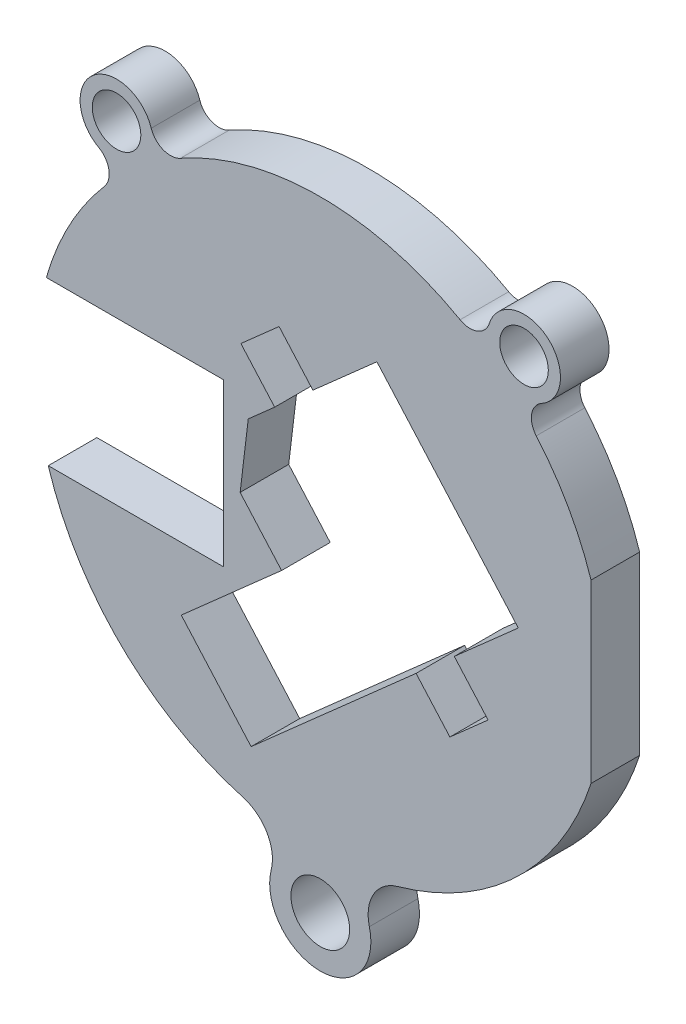
SolidWorks part; units mm, degrees
ref_plane "Front Plane" through (0, 0, 0) normal (0, 0, 1) x (1, 0, 0)
ref_plane "Top Plane" through (0, 0, 0) normal (0, 1, 0) x (1, 0, 0)
ref_plane "Right Plane" through (0, 0, 0) normal (1, 0, 0) x (0, 0, -1)
sketch "Sketch1" plane through (0, 0, 0) normal (0, 0, 1) x (1, 0, 0)
  line L0 (-21.141, 18.2245) -> (20.1141, 18.2245) construction
  line L1 (-4.8006, 1.8415) -> (-4.8006, -3.0861)
  line L2 (-4.8006, -3.0861) -> (-8.9662, -3.0861)
  line L3 (-8.9662, -3.0861) -> (-8.9662, -5.3514)
  line L4 (-8.9662, -5.3514) -> (-6.5786, -5.3514)
  line L5 (-4.9806, 7.3918) -> (-2.5835, 9.5123)
  line L6 (-2.5835, 9.5123) -> (-0.463, 7.1152)
  line L7 (-4.9806, 7.3918) -> (-2.8601, 4.9947)
  line L8 (3.2088, 10.3632) -> (-4.5153, 3.5306)
  line L9 (12.0777, 0.3371) -> (4.3536, -6.4955)
  line L10 (-4.5153, 3.5306) -> (-5.0276, -0.7207)
  line L11 (-5.0276, -0.7207) -> (0.0716, -6.4852)
  line L12 (0.0716, -6.4852) -> (4.3536, -6.4955)
  line L13 (-2.478, -3.6029) -> (7.6432, 5.3502) construction
  line L14 (3.2088, 10.3632) -> (12.0777, 0.3371)
  line L15 (3.2088, 10.3632) -> (11.8761, 18.0302)
  line L16 (-9.2588, -8.622) -> (-4.7522, -4.6355) construction
  line L17 (-9.2588, -8.622) -> (-5.994, -12.3128) construction
  line L18 (-4.7522, -4.6355) -> (-1.4874, -8.3263) construction
  line L19 (-5.994, -12.3128) -> (-1.4874, -8.3263) construction
  line L20 (12.0777, 0.3371) -> (20.228, 7.5468)
  line L21 (-6.5786, -5.3514) -> (-6.5786, -5.8039)
  line L22 (-6.5786, -5.8039) -> (-14.0208, -5.8039)
  line L23 (-14.0208, -5.8039) -> (-14.0208, 4.5593)
  line L24 (-14.0208, 4.5593) -> (-6.5786, 4.5593)
  line L25 (-6.5786, 4.5593) -> (-6.5786, 3.9924)
  line L26 (-6.5786, 3.9924) -> (-8.9662, 3.9924)
  line L27 (-8.9662, 3.9924) -> (-8.9662, 1.8415)
  line L28 (-8.9662, 1.8415) -> (-4.8006, 1.8415)
  line L29 (8.4059, -2.9109) -> (10.5264, -5.308)
  line L30 (10.5264, -5.308) -> (8.1292, -7.4285)
  line L31 (8.1292, -7.4285) -> (6.0088, -5.0313)
  line L32 (-4.7522, -4.6355) -> (-2.9639, -3.0536) construction
  line L33 (-1.4874, -8.3263) -> (0.5926, -6.4864) construction
  line L34 (-5.4555, -12.9216) -> (-0.9489, -8.9351)
  line L35 (-8.7203, -9.2308) -> (-4.2137, -5.2443)
  line L36 (-8.7203, -9.2308) -> (-5.4555, -12.9216)
  line L37 (-0.9489, -8.9351) -> (1.816, -6.4894)
  line L38 (-4.2137, -5.2443) -> (-2.4254, -3.6624)
  arc A0 (-15.2315, -0.5079) -> (3.302, 14.878) centre (0, 0) ccw construction
  circle A1 centre (0, 0) radius 21.59 construction
  circle A2 centre (0, 0) radius 21.59
  circle A3 centre (0, -18.415) radius 1.4224 construction
  circle A4 centre (0, 18.415) radius 1.4224 construction
  circle A5 centre (0, -18.415) radius 1.4224
  circle A6 centre (0, 18.415) radius 1.4224
  circle A7 centre (0, 0) radius 15.24
  dimension "D3" = 30.48
  dimension "D1" = 33.4645
  dimension "D2" = 20.0406
  dimension "D4" = 4.9276
  dimension "D5" = 2.7178
  dimension "D6" = 8.7122
  dimension "D7" = 7.8613
  dimension "D8" = 2.7178
  dimension "D9" = 3.2004
  dimension "D10" = 13.3858
  dimension "D11" = 3.1623
  dimension "D12" = 10.3124
  dimension "D13" = 8.6106
  dimension "D14" = 7.6962
  dimension "D15" = 6.0168
  dimension "D16" = 2.3876
  dimension "D17" = 4.9276
  dimension "D18" = 22.86
  dimension "D19" = 7.4422
  dimension "D20" = 5.0546
  dimension "D21" = 13.6652
  dimension "D22" = 29.2608
  dimension "D23" = 0.8128
extrude "Boss-Extrude1" add sketch "Sketch1" along normal blind 3.048 contours L15 A7 L20 L9 L29 L30 L31 L12 L33 L19 L17 L16 L32 L11 L1 L2 L3 L4 L21 L22 L23 L24 L25 L26 L27 L28 L10 L8 L7 L5 L6 | L28 L27 L26 L25 L24 L23 L22 L21 L4 L3 L2 L1 L11 L10 | A7 L15 A2 L20 A6 A5 region at (-6.8834, 2.2726, 0) region at (-10.1343, -0.6067, 0) region at (-13.5004, -8.3055, 0)
sketch "Sketch2" plane through (0, 0, 3.048) normal (0, 0, 1) x (1, 0, 0)
  line L0 (-5.0276, 2.3876) -> (-5.0276, -2.794)
  line L1 (-5.0276, 2.3876) -> (-10.4871, 2.3876)
  line L2 (-10.4871, 2.3876) -> (-10.4871, 3.8608)
  line L3 (-10.4871, 3.8608) -> (-7.085, 3.8608)
  line L4 (-7.085, 3.8608) -> (-7.085, 4.8768)
  line L5 (-7.085, 4.8768) -> (-14.4764, 4.8768)
  line L6 (-14.4764, 4.8768) -> (-14.4764, -5.2832)
  line L7 (-14.4764, -5.2832) -> (-7.085, -5.2832)
  line L8 (-7.085, -5.2832) -> (-7.085, -4.2672)
  line L9 (-7.085, -4.2672) -> (-10.4871, -4.2672)
  line L10 (-10.4871, -4.2672) -> (-10.4871, -2.794)
  line L11 (-10.4871, -2.794) -> (-5.0276, -2.794)
  line L12 (-5.0276, 2.3876) -> (-4.653, 2.3876)
  line L13 (-4.5153, 3.5306) -> (-5.0276, -0.7207) construction
  line L14 (-5.0276, -2.794) -> (-3.1935, -2.794)
  line L15 (-5.0276, -0.7207) -> (-2.4254, -3.6624) construction
  line L16 (-7.085, 3.8608) -> (-7.085, -4.2672)
  line L17 (-14.4764, 4.8768) -> (-21.032, 4.8768)
  line L18 (-14.4764, -5.2832) -> (-20.9336, -5.2832)
  arc A0 (11.8761, 18.0302) -> (20.228, 7.5468) centre (0, 0) ccw construction
  arc M2 (11.8761, 18.0302) -> (20.228, 7.5468) centre (0, 0) ccw
  dimension "D1" = 9.4488
  dimension "D2" = 7.3914
  dimension "D3" = 10.16
  dimension "D4" = 1.016
  dimension "D5" = 5.1816
  dimension "D6" = 5.4596
  dimension "D7" = 1.4732
  dimension "D8" = 1.143
extrude "Cut-Extrude3" cut sketch "Sketch2" against normal through all contours L10 L11 L0 L1 L2 L3 L4 L5 L6 L7 L8 L9 | L16 L3 L2 L1 | L16 L11 L10 L9 | L18 L6 L17 M2 region at (-11.0879, -0.2032, 3.048) region at (-8.7861, 3.1242, 3.048) region at (-8.7861, -3.5306, 3.048) region at (-17.9346, -0.1913, 3.048)
sketch "Sketch3" plane through (0, 0, 0) normal (0, 0, -1) x (-1, 0, 0)
  line L0 (-20.8712, -5.5245) -> (-16.9841, -5.5245)
  line L1 (-16.9841, -5.5245) -> (-20.8712, -5.5245) construction
  line L2 (-16.9841, -5.5245) -> (-16.9841, 4.6772)
  line L3 (-8.4059, -2.9109) -> (-20.228, 7.5468) construction
  line L4 (-16.9841, 5.5245) -> (-16.9841, -5.5245) construction
  line L5 (-16.9841, 4.6772) -> (-20.228, 7.5468)
  arc A0 (-20.228, 7.5468) -> (20.9336, -5.2832) centre (0, 0) ccw construction
  arc A1 (-20.228, 7.5468) -> (-20.8712, -5.5245) centre (0, 0) ccw
  arc A2 (-20.8712, -5.5245) -> (-20.8712, 5.5245) centre (0, 0) ccw construction
extrude "Cut-Extrude4" cut sketch "Sketch3" against normal through all
sketch "Sketch4" plane through (0, 0, 0) normal (0, 0, -1) x (-1, 0, 0)
  line L0 (-12.3201, -16.1591) -> (12.3201, 16.1591) construction
  line L1 (-13.8351, -15.0041) -> (10.8052, 17.3141)
  line L2 (-10.8052, -17.3141) -> (13.8351, 15.0041)
  line L3 (-16.1591, 12.3201) -> (16.1591, -12.3201) construction
  line L4 (-15.0041, 13.8351) -> (17.3141, -10.8052)
  line L5 (-17.3141, 10.8052) -> (15.0041, -13.8351)
  line L6 (-16.9841, 5.5245) -> (-16.9841, 4.6772)
  line L7 (-16.9841, 4.6772) -> (-12.4201, 0.64)
  line L8 (-8.4059, -2.9109) -> (-16.9841, 4.6772) construction
  line L9 (-12.4201, 0.64) -> (-3.5512, 10.6661)
  line L10 (0.463, 7.1152) -> (-11.8761, 18.0302) construction
  line L11 (-3.5512, 10.6661) -> (-8.9594, 15.4501)
  line L12 (5.0276, -0.7207) -> (2.4254, -3.6624) construction
  line L13 (0, 0) -> (2.7145, -20.1379) construction
  line L14 (1.8879, 0.2545) -> (4.6025, -19.8834)
  line L15 (-1.8879, -0.2545) -> (0.8266, -20.3924)
  line L16 (-16.1591, 12.3201) -> (12.3201, 16.1591) construction
  circle A0 centre (0, 0) radius 17.86
  arc A1 (-13.8351, -15.0041) -> (-10.8052, -17.3141) centre (-12.3201, -16.1591) ccw
  arc A2 (13.8351, 15.0041) -> (10.8052, 17.3141) centre (12.3201, 16.1591) ccw
  arc A3 (-15.0041, 13.8351) -> (-17.3141, 10.8052) centre (-16.1591, 12.3201) ccw
  arc A4 (15.0041, -13.8351) -> (17.3141, -10.8052) centre (16.1591, -12.3201) ccw
  circle A5 centre (12.3201, 16.1591) radius 1.1049
  circle A6 centre (16.1591, -12.3201) radius 1.1049
  circle A7 centre (-12.3201, -16.1591) radius 1.1049
  circle A8 centre (-16.1591, 12.3201) radius 1.1049
  arc A9 (1.8879, 0.2545) -> (-1.8879, -0.2545) centre (0, 0) ccw
  arc A10 (0.8266, -20.3924) -> (4.6025, -19.8834) centre (2.7145, -20.1379) ccw
  arc A11 (2.7145, -20.1379) -> (16.1591, -12.3201) centre (0, 0) ccw construction
  circle A12 centre (2.7145, -20.1379) radius 1.1049
  point P6 (0, 0)
  point P13 (0, 0)
  point P39 (1.3573, -10.0689)
  line M1 (-8.4059, -2.9109) -> (-16.9841, 4.6772)
  line M3 (-16.9841, -5.5245) -> (-20.8712, -5.5245)
  arc M4 (-20.8712, -5.5245) -> (20.9336, -5.2832) centre (0, 0) ccw
  line M5 (20.9336, -5.2832) -> (7.085, -5.2832)
  line M7 (7.085, 4.8768) -> (21.032, 4.8768)
  arc M8 (21.032, 4.8768) -> (-11.8761, 18.0302) centre (0, 0) ccw
  line M9 (-11.8761, 18.0302) -> (0.463, 7.1152)
  circle M24 centre (0, 18.415) radius 1.4224
  circle M25 centre (0, -18.415) radius 1.4224
  dimension "D1" = 3.81
  dimension "D2" = 3.81
  dimension "D3" = 13.97
extrude "Boss-Extrude2" add sketch "Sketch4" against normal up to vertex (3.048 mm away) contours A0 L4 L9 M9 | L4 A0 L5 L9 | L5 A0 L6 L9 M1 | L4 A3 L5 A0 A8 | A2 L1 A0 L2 A5 M8 | A0 M24 | A0 M25 | A0 L15 M25 | L15 A0 M25 | A10 M4 | A2 M8 region at (13.4131, 4.8762, 0) region at (10.9588, 8.3691, 0) region at (16.2523, 10.0852, 0) region at (0.2829, -17.4804, 0) region at (-2.9174, -21.6425, 0) region at (8.1323, 11.4955, 0) region at (-0.7535, -17.5272, 0) region at (-0.9598, -18.5708, 0) region at (-10.0849, 16.2525, 0) region at (0, 17.4932, 0) region at (-13.2407, 17.3665, 0) up to point (10.5264, -5.308, 3.048)
extrude "Cut-Extrude5" cut sketch "Sketch4<3>" against normal through all contours A4 L5 A0 L2 A1 M25 M4 | A4 A0 L4 M4 M5 | A1 L1 A0 M3 M4 | A7 | A6 | A5 | A2 L2 A0 M7 M8 | A2 A0 L1 M8 M9 M24 | L1 A1 L2 A0 A7 M4 | A10 A4 L5 A0 L14 M4 | A4 L4 A0 L5 A6 M4 | A12 region at (16.6582, -10.306, 0) region at (13.002, -14.0284, 0) region at (5.4053, -18.8788, 0) region at (-9.8123, -16.8747, 0) region at (-5.4955, 17.2518, 0) region at (-15.6105, -14.0703, 0) region at (-16.798, 10.0037, 0) region at (-18.1332, -7.9591, 0) region at (-12.3201, 16.1591, 0) region at (-16.1591, -12.3201, 0) region at (12.3201, -16.1591, 0) region at (-2.7145, -20.1379, 0)
sketch "Sketch4<3>" plane through (0, 0, 0) normal (0, 0, -1) x (-1, 0, 0) same geometry as "Sketch4"
sketch "Sketch5" plane through (0, 0, 3.048) normal (0, 0, 1) x (1, 0, 0)
  line L0 (4.3536, -6.4955) -> (-4.3384, -14.1843)
  line L1 (-4.3384, -14.1843) -> (-5.4555, -12.9216)
  line L2 (-8.7203, -9.2308) -> (-5.4555, -12.9216) construction
  line L3 (6.0088, -5.0313) -> (4.3536, -6.4955) construction
  line L4 (-5.4555, -12.9216) -> (1.816, -6.4894)
  line L5 (1.816, -6.4894) -> (4.3536, -6.4955)
extrude "Cut-Extrude10" cut sketch "Sketch5" against normal through all
sketch "Sketch6" plane through (0, 0, 3.048) normal (0, 0, 1) x (1, 0, 0)
  line L0 (17.3141, 10.8052) -> (15.2768, 9.2519) construction
  line L1 (15.0041, 13.8351) -> (12.9668, 12.2818) construction
  line L2 (17.3141, 10.8052) -> (15.2768, 9.2519)
  line L3 (15.0041, 13.8351) -> (12.9668, 12.2818)
  line L4 (17.5451, 10.5023) -> (15.472, 8.9216)
  line L5 (14.7731, 14.138) -> (12.7, 12.5574)
  line L23 (-4.9801, -19.8325) -> (-4.6378, -17.2935)
  line L24 (-0.1068, -17.9043) -> (-0.449, -20.4433)
  line L25 (-4.9801, -19.8325) -> (-4.6318, -17.2489)
  line L26 (-0.1008, -17.8597) -> (-0.449, -20.4433)
  line L29 (14.7731, 14.138) -> (12.7358, 12.5847) construction
  line L30 (17.5451, 10.5023) -> (15.5078, 8.9489) construction
  line L31 (-14.138, 14.7731) -> (-12.5847, 12.7358)
  line L32 (-8.9489, 15.5078) -> (-10.5023, 17.5451)
  line L33 (-14.138, 14.7731) -> (-12.5574, 12.7)
  line L34 (-8.9216, 15.472) -> (-10.5023, 17.5451)
  arc A0 (17.3141, 10.8052) -> (15.0041, 13.8351) centre (16.1591, 12.3201) ccw construction
  arc A1 (17.3141, 10.8052) -> (15.0041, 13.8351) centre (16.1591, 12.3201) ccw
  arc A2 (17.5451, 10.5023) -> (14.7731, 14.138) centre (16.1591, 12.3201) ccw
  arc A11 (-4.9801, -19.8325) -> (-0.449, -20.4433) centre (-2.7145, -20.1379) ccw
  arc A12 (-4.9801, -19.8325) -> (-0.449, -20.4433) centre (-2.7145, -20.1379) ccw
  circle A14 centre (0, 0) radius 17.86
  arc A15 (-10.5023, 17.5451) -> (-14.138, 14.7731) centre (-12.3201, 16.1591) ccw
  arc A16 (-10.5023, 17.5451) -> (-14.138, 14.7731) centre (-12.3201, 16.1591) ccw
  line M25 (-4.2602, -17.3444) -> (-4.6025, -19.8834)
  arc M26 (-4.6025, -19.8834) -> (-0.8266, -20.3924) centre (-2.7145, -20.1379) ccw
  line M27 (-0.8266, -20.3924) -> (-0.4844, -17.8534)
  arc M28 (-0.4844, -17.8534) -> (16.9841, -5.5245) centre (0, 0) ccw
  arc M30 (16.9841, 5.5245) -> (15.2768, 9.2519) centre (0, 0) ccw
  line M31 (15.2768, 9.2519) -> (17.3141, 10.8052)
  arc M32 (17.3141, 10.8052) -> (15.0041, 13.8351) centre (16.1591, 12.3201) ccw
  line M33 (15.0041, 13.8351) -> (12.9668, 12.2818)
  arc M34 (12.9668, 12.2818) -> (-9.2519, 15.2768) centre (0, 0) ccw
  line M35 (-9.2519, 15.2768) -> (-10.8052, 17.3141)
  arc M36 (-10.8052, 17.3141) -> (-13.8351, 15.0041) centre (-12.3201, 16.1591) ccw
  line M37 (-13.8351, 15.0041) -> (-12.2818, 12.9668)
  arc M38 (-12.2818, 12.9668) -> (-17.1812, 4.8768) centre (0, 0) ccw
  arc M42 (-17.0607, -5.2832) -> (-4.2602, -17.3444) centre (0, 0) ccw
  dimension "D1" = 0.381
  dimension "D2" = 0.381
  dimension "D3" = 0.381
extrude "Boss-Extrude3" add sketch "Sketch6" against normal up to vertex contours L34 A16 L33 M38 M37 M36 M35 M34 | L25 A12 L26 M28 M27 M26 M25 M42 | L4 A2 L5 M34 M33 M32 M31 M30 region at (17.7383, 13.5242, 3.048) region at (-9.1284, 15.4449, 3.048) region at (-0.1744, -17.8725, 3.048) up to point (8.4059, -2.9109, 0)
sketch "Sketch7" plane through (0, 0, 0) normal (0, 0, -1) x (-1, 0, 0)
  line L0 (7.085, 4.8768) -> (6.0563, 4.8768)
  line L1 (6.0563, 4.8768) -> (6.0563, -5.2832)
  line L2 (6.0563, -5.2832) -> (7.085, -5.2832)
  line L3 (5.0276, -0.7207) -> (7.085, -0.7207) construction
  line L4 (7.085, 4.8768) -> (7.085, -5.2832) construction
  line L5 (7.085, 4.8768) -> (7.085, -5.2832)
  point P11 (6.0563, -0.7207)
extrude "Cut-Extrude11" cut sketch "Sketch7" against normal through all
sketch "Sketch8" plane through (0, 0, 3.048) normal (0, 0, 1) x (1, 0, 0)
  circle A0 centre (0, 0) radius 17.86
  circle A1 centre (0, 0) radius 23.4976
extrude "Cut-Extrude12" cut sketch "Sketch8" against normal through all
sketch "Sketch9" plane through (0, 0, 3.048) normal (0, 0, 1) x (1, 0, 0)
  line L0 (0, 17.86) -> (-14.5094, 17.86) construction
  circle A0 centre (12.7793, 15.574) radius 1.524
  circle A1 centre (12.7793, 15.574) radius 2.286
  circle A2 centre (14.5094, 12.4672) radius 1.27
  circle A3 centre (9.3946, 16.6642) radius 1.27
  circle A4 centre (-12.7793, 15.574) radius 2.286
  circle A5 centre (-9.3946, 16.6642) radius 1.27
  circle A6 centre (-14.5094, 12.4672) radius 1.27
  circle A7 centre (0, -21.035) radius 1.8415
  circle A8 centre (0, -21.035) radius 3.175
  circle A9 centre (5.5404, -19.6332) radius 2.54
  circle A10 centre (-5.5404, -19.6332) radius 2.54
  circle A11 centre (-12.7793, 15.574) radius 1.524
  circle A12 centre (0, 0) radius 17.86
  circle A13 centre (0, 0) radius 17.86
  arc A14 (16.9841, 5.5245) -> (-17.1812, 4.8768) centre (0, 0) ccw construction
  arc M17 (16.9841, 5.5245) -> (-17.1812, 4.8768) centre (0, 0) ccw
  arc M21 (-17.0607, -5.2832) -> (16.9841, -5.5245) centre (0, 0) ccw
  dimension "D1" = 3.048
  dimension "D2" = 4.572
  dimension "D3" = 2.54
  dimension "D4" = 2.54
  dimension "D5" = 3.683
  dimension "D6" = 6.35
  dimension "D7" = 5.08
extrude "Boss-Extrude4" add sketch "Sketch9" against normal up to vertex contours A2 A1 M17 | A1 A0 | A3 A1 M17 | A6 A4 M17 | A4 A11 | A5 A4 M17 | A8 A7 | A10 A8 M21 | A9 A8 M21 region at (14.6944, 14.4484, 3.048) region at (10.1667, 15.1037, 3.048) region at (12.8282, 12.9198, 3.048) region at (-10.1667, 15.1037, 3.048) region at (-10.5849, 15.9187, 3.048) region at (-12.8282, 12.9198, 3.048) region at (2.6103, -18.2487, 3.048) region at (3.0615, -20.6537, 3.048) region at (-2.6103, -18.2487, 3.048) up to point (-0.463, 7.1152, 0)
